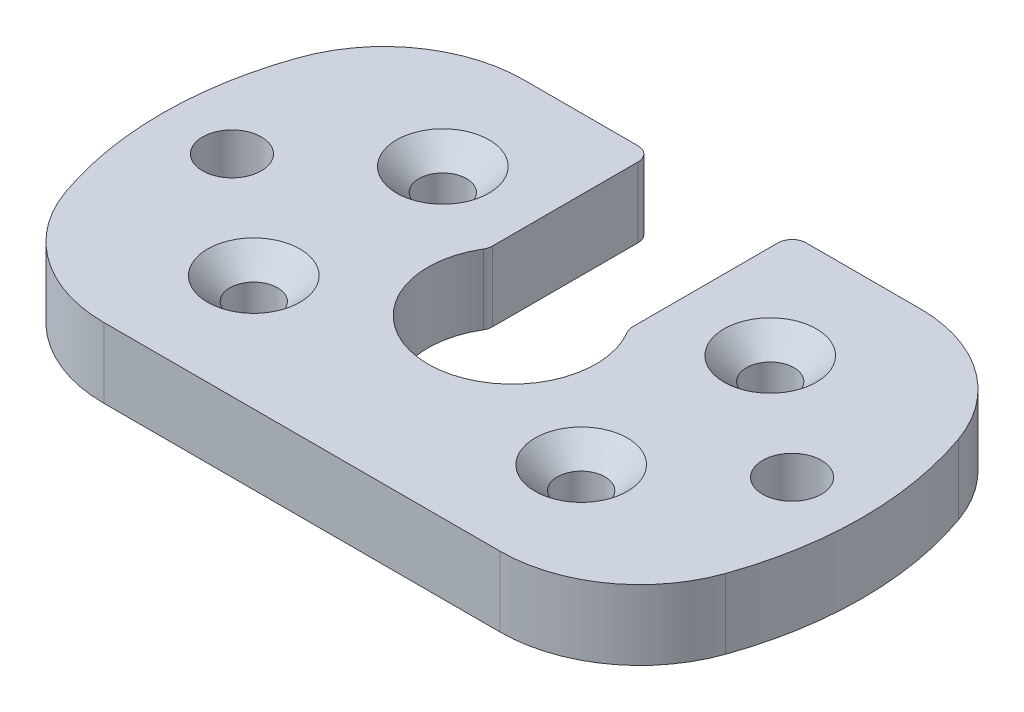
SolidWorks part; units mm, degrees
material "5052-H32"
ref_plane "前视基准面" through (0, 0, 0) normal (0, 0, 1) x (1, 0, 0)
ref_plane "上视基准面" through (0, 0, 0) normal (0, 1, 0) x (1, 0, 0)
ref_plane "右视基准面" through (0, 0, 0) normal (1, 0, 0) x (0, 0, -1)
other "Configuration Table"
sketch "草图1" plane through (0, 0, 0) normal (0, 1, 0) x (1, 0, 0)
  circle A0 centre (0, 0) radius 25
  dimension "D1" = 50
extrude "凸台-拉伸1" add sketch "草图1" along normal blind 5
sketch "草图2" plane through (0, 5, 0) normal (0, 1, 0) x (1, 0, 0)
  circle A0 centre (0, 13.5) radius 1 construction
  circle A1 centre (0, 0) radius 13.5 construction
  circle A2 centre (11.6913, 6.75) radius 1
  circle A3 centre (11.6913, -6.75) radius 1
  circle A4 centre (0, -13.5) radius 1 construction
  circle A5 centre (-11.6913, -6.75) radius 1
  circle A6 centre (-11.6913, 6.75) radius 1
  point P18 (0, 0)
  dimension "D1" = 27
  dimension "D3" = 2
  dimension "D2" = 6
extrude "切除-拉伸1" cut sketch "草图2" against normal blind 4
hole_wizard "M3 十字槽沉头木螺钉的锥形沉头孔1" positions "3D草图1" profile "草图3" countersink size "M3" standard "GB"
sketch3d "3D草图1"
  circle A1 centre (-11.6913, 5, -6.75) radius 1 construction
  circle A2 centre (-11.6913, 5, 6.75) radius 1 construction
  circle A4 centre (11.6913, 5, 6.75) radius 1 construction
  circle A5 centre (11.6913, 5, -6.75) radius 1 construction
  point P2 (11.6913, 5, -6.75)
  point P4 (11.6913, 5, 6.75)
  point P8 (-11.6913, 5, 6.75)
  point P10 (-11.6913, 5, -6.75)
  point P18 (-11.6913, 6, -6.75)
  point P22 (-11.6913, 6, 6.75)
  point P30 (11.6913, 6, 6.75)
  point P33 (11.6913, 6, -6.75)
sketch "草图3" plane through (11.6913, 5, -6.75) normal (1, 0, 0) x (0, 0, 1)
  line L0 (0, 0) -> (0, 8.5215)
  line L1 (0, 8.5215) -> (1.7, 7.5)
  line L2 (1.7, 7.5) -> (1.7, 1.6)
  line L3 (1.7, 1.6) -> (3.3, 0)
  line L5 (3.3, 0) -> (0, 0)
  line L6 (-1.7, 1.6) -> (-3.3, 0) construction
  line L10 (0, 8.5215) -> (-1.7, 7.5) construction
  line L11 (0, -6.35) -> (0, 107.95) construction
  dimension "孔直径" = 3.4
  dimension "孔深度" = 7.5
  dimension "近端锥形沉头孔直径" = 6.6
  dimension "近端锥形沉头孔角度" = 90
  dimension "导头角度" = 118
sketch "草图4" plane through (0, 5, 0) normal (0, 1, 0) x (1, 0, 0)
  line L0 (0, -2.75) -> (0, 2.75) construction
  circle A1 centre (-20, 0) radius 2
  circle A2 centre (20, 0) radius 2
  dimension "D1" = 4
  dimension "D2" = 40
extrude "切除-拉伸2" cut sketch "草图4" against normal blind 4
hole_wizard "M5 螺纹孔1" positions "3D草图3" profile "草图6" tap size "M5" standard "GB"
sketch3d "3D草图3"
  circle A0 centre (-20, 5, 0) radius 2 construction
  circle A1 centre (20, 5, 0) radius 2 construction
  point P0 (-20, 5, 0)
  point P2 (20, 5, 0)
  point P7 (-20, 7, 0)
  point P11 (20, 7, 0)
sketch "草图6" plane through (-20, 5, 0) normal (1, 0, 0) x (0, 0, 1)
  line L0 (0, 0) -> (0, 13.6618)
  line L1 (0, 13.6618) -> (2.1, 12.4)
  line L2 (2.1, 12.4) -> (2.1, 0)
  line L5 (2.1, 0) -> (0, 0)
  line L10 (0, 13.6618) -> (-2.1, 12.4) construction
  line L11 (0, -6.35) -> (0, 107.95) construction
  dimension "螺纹孔钻头直径" = 4.2
  dimension "螺纹孔钻头深度" = 12.4
  dimension "导头角度" = 118
cosmetic thread "孔螺蚊线1" parameters "D1"=10, "D2"=5
cosmetic thread "孔螺蚊线2" parameters "D1"=10, "D2"=5
sketch "草图7" plane through (0, 5, 0) normal (0, 1, 0) x (1, 0, 0)
  line L0 (-2.75, 0) -> (2.75, 0) construction
  line L1 (-39.166, 25) -> (39.166, 25)
  line L2 (-39.166, 25) -> (-39.166, 15)
  line L3 (-39.166, 15) -> (39.166, 15)
  line L4 (39.166, 25) -> (39.166, 15)
  line L5 (-39.166, -15) -> (39.166, -15)
  line L6 (39.166, -25) -> (39.166, -15)
  line L7 (-39.166, -25) -> (39.166, -25)
  line L8 (-39.166, -25) -> (-39.166, -15)
  circle A0 centre (0, 0) radius 25 construction
  point P6 (0, 25)
  dimension "D1" = 10
extrude "切除-拉伸3" cut sketch "草图7" against normal through all
fillet "圆角1" radius 10 4 edges at (20, 2.5, -15) (20, 2.5, 15) (-20, 2.5, -15) (-20, 2.5, 15)
ref_axis "基准轴1" through (0, 0, 0) along (1, 0, 0)
sketch "草图9" plane through (0, 5, 0) normal (0, 1, 0) x (1, 0, 0)
  circle A0 centre (0, 0) radius 6
  dimension "D1" = 12
extrude "切除-拉伸5" cut sketch "草图9" against normal blind 10
sketch "草图10" plane through (0, 5, 0) normal (0, 1, 0) x (1, 0, 0)
  line L0 (-14.1421, 15) -> (14.1421, 15) construction
  line L1 (-5, 15) -> (5, 15)
  line L2 (-5, 15) -> (-5, 3.3166)
  line L3 (-5, 3.3166) -> (5, 3.3166)
  line L4 (5, 15) -> (5, 3.3166)
  circle A0 centre (0, 0) radius 6 construction
  point P6 (0, 15)
  point P7 (0, 15)
  dimension "D1" = 10
extrude "切除-拉伸6" cut sketch "草图10" against normal blind 10
fillet "圆角2" radius 1 4 edges at (5, 2.5, -3.3166) (-5, 2.5, -3.3166) (5, 2.5, -15) (-5, 2.5, -15)
